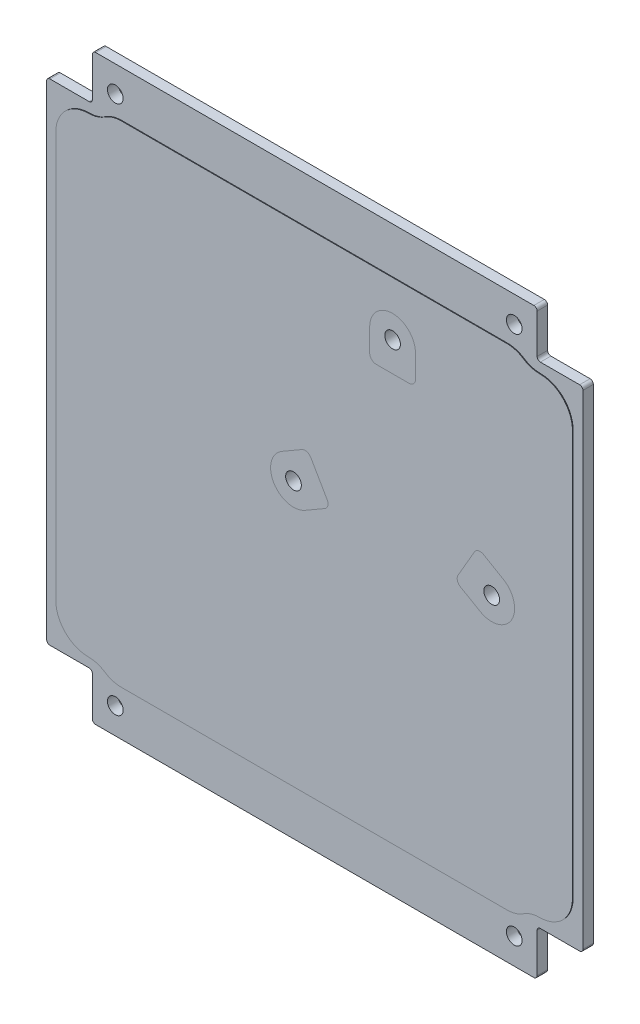
SolidWorks part; units mm, degrees
material "PET"
ref_plane "Front Plane" through (0, 0, 0) normal (0, 0, 1) x (1, 0, 0)
ref_plane "Top Plane" through (0, 0, 0) normal (0, 1, 0) x (1, 0, 0)
ref_plane "Right Plane" through (0, 0, 0) normal (1, 0, 0) x (0, 0, -1)
sketch "Sketch1" plane through (0, 0, 0) normal (0, 0, 1) x (1, 0, 0)
  line L0 (-34, 44) -> (-34, 38)
  line L1 (-33.5, -44.5) -> (33.5, -44.5)
  line L2 (-41, 37) -> (-41, -37)
  line L3 (-33.5, 44.5) -> (33.5, 44.5)
  line L4 (41, -37) -> (41, 37)
  line L5 (34, -44) -> (34, -38)
  line L6 (34.5, -37.5) -> (40.5, -37.5)
  line L7 (-34.5, 37.5) -> (-40.5, 37.5)
  line L8 (34, 44) -> (34, 38)
  line L9 (34.5, 37.5) -> (40.5, 37.5)
  line L10 (-40.5, -37.5) -> (-34.5, -37.5)
  line L11 (-34, -38) -> (-34, -44)
  line L12 (-34.5, -38) -> (34.5, 38) construction
  line L13 (34.5, -38) -> (-34.5, 38) construction
  arc A0 (-33.5, 44.5) -> (-34, 44) centre (-33.5, 44) ccw
  arc A1 (33.5, 44.5) -> (34, 44) centre (33.5, 44) cw
  arc A2 (34, 38) -> (34.5, 37.5) centre (34.5, 38) ccw
  arc A3 (40.5, 37.5) -> (41, 37) centre (40.5, 37) cw
  arc A4 (33.5, -44.5) -> (34, -44) centre (33.5, -44) ccw
  arc A5 (34.5, -37.5) -> (34, -38) centre (34.5, -38) ccw
  arc A6 (40.5, -37.5) -> (41, -37) centre (40.5, -37) ccw
  arc A7 (-34, -44) -> (-33.5, -44.5) centre (-33.5, -44) ccw
  arc A8 (-34, -38) -> (-34.5, -37.5) centre (-34.5, -38) ccw
  arc A9 (-41, -37) -> (-40.5, -37.5) centre (-40.5, -37) ccw
  arc A10 (-40.5, 37.5) -> (-41, 37) centre (-40.5, 37) ccw
  arc A11 (-34.5, 37.5) -> (-34, 38) centre (-34.5, 38) ccw
  point P0 (0, 0)
  dimension "D4" = 0.5
  dimension "D1" = 7
  dimension "D2" = 7
  dimension "D3" = 7
  dimension "D5" = 7
  dimension "D6" = 7
  dimension "D7" = 7
  dimension "D8" = 7
  dimension "D9" = 7
  dimension "D10" = 89
  dimension "D11" = 82
extrude "Boss-Extrude1" add sketch "Sketch1" along normal blind 1.6
sketch "Esboço1" plane through (0, 0, 1.6) normal (0, 0, 1) x (1, 0, 0)
  line L0 (11.8117, 0) -> (-11.978, 0) construction
  line L1 (-29.5, -37.5) -> (29.5, -37.5)
  line L2 (0, 10.1561) -> (0, -5.0161) construction
  line L3 (-29.5, 37.5) -> (29.5, 37.5)
  line L5 (-29.5, -32.5) -> (29.5, 32.5) construction
  line L6 (-29.5, 32.5) -> (29.5, -32.5) construction
  line L8 (-39.5, -31) -> (-39.5, 31)
  line L10 (39.5, -31) -> (39.5, 31)
  line L11 (-39.5, -36) -> (39.5, 36) construction
  line L12 (-39.5, 36) -> (39.5, -36) construction
  arc A0 (-34.5, 36) -> (-32, 36.75) centre (-34.5, 40.5417) ccw
  arc A1 (-29.5, 37.5) -> (-32, 36.75) centre (-29.5, 32.9583) ccw
  arc A2 (-29.5, -37.5) -> (-32, -36.75) centre (-29.5, -32.9583) cw
  arc A3 (-34.5, -36) -> (-32, -36.75) centre (-34.5, -40.5417) cw
  arc A4 (34.5, 36) -> (39.5, 31) centre (34.5, 31) cw
  arc A5 (34.5, -36) -> (39.5, -31) centre (34.5, -31) ccw
  arc A6 (-34.5, -36) -> (-39.5, -31) centre (-34.5, -31) cw
  arc A7 (-39.5, 31) -> (-34.5, 36) centre (-34.5, 31) cw
  arc A8 (29.5, -37.5) -> (32, -36.75) centre (29.5, -32.9583) ccw
  arc A9 (34.5, -36) -> (32, -36.75) centre (34.5, -40.5417) ccw
  arc A10 (29.5, 37.5) -> (32, 36.75) centre (29.5, 32.9583) cw
  arc A11 (34.5, 36) -> (32, 36.75) centre (34.5, 40.5417) cw
  point P0 (0, 0)
  point P1 (0, 0)
  dimension "D2" = 5
  dimension "D3" = 75
  dimension "D5" = 79
extrude "Boss-Extrude2" add sketch "Esboço1" along normal blind 0.1
hole_wizard "M2 Hole1-FixingStructure" positions "Sketch3" profile "Sketch2" hole size "M2" standard "DIN"
sketch "Sketch3" plane through (0, 0, 0) normal (0, 0, -1) x (-1, 0, 0)
  line L0 (-33.5, 44.5) -> (33.5, 44.5) construction
  line L1 (33.5, -44.5) -> (-33.5, -44.5) construction
  line L2 (-41, -37) -> (-41, 37) construction
  line L3 (41, 37) -> (41, -37) construction
  point P0 (-30.5, 40.5)
  point P2 (30.5, 40.5)
  point P4 (-30.5, -40.5)
  point P6 (30.5, -40.5)
  dimension "D1" = 4
  dimension "D2" = 4
  dimension "D3" = 10.5
  dimension "D4" = 10.5
sketch "Sketch2" plane through (30.5, 40.5, 0) normal (1, 0, 0) x (0, 1, 0)
  line L0 (0, 0) -> (0, 200.721)
  line L1 (0, 200.721) -> (1.2, 200)
  line L2 (1.2, 200) -> (1.2, 0)
  line L5 (1.2, 0) -> (0, 0)
  line L10 (0, 200.721) -> (-1.2, 200) construction
  line L11 (0, -6.35) -> (0, 107.95) construction
  dimension "Hole Dia." = 2.4
  dimension "Hole Depth" = 200
  dimension "Drill Angle" = 118
sketch "Sketch4" plane through (0, 0, 1.7) normal (0, 0, 1) x (1, 0, 0)
  circle A0 centre (27.1554, 3) radius 1.2 construction
  circle A1 centre (-3.1554, 3) radius 1.2 construction
  circle A2 centre (12, 29.25) radius 1.2 construction
  circle A3 centre (27.1554, 3) radius 1.2
  circle A4 centre (-3.1554, 3) radius 1.2
  circle A5 centre (12, 29.25) radius 1.2
extrude "Cut-Extrude1" cut sketch "Sketch4" against normal up to surface (1.7 mm away) up to face at (29.3, 40.5, 0)
sketch "Sketch5" plane through (0, 0, 1.7) normal (0, 0, 1) x (1, 0, 0)
  line L4 (1.6256, 1.7189) -> (-1.4054, -0.0311)
  line L5 (26.7404, 7.2811) -> (28.9054, 6.0311)
  line L6 (25.4054, -0.0311) -> (23.2404, 1.2189)
  line L7 (25.8744, 7.7811) -> (28.9054, 6.0311)
  line L8 (25.4054, -0.0311) -> (22.3744, 1.7189)
  line L9 (22.0083, 3.0849) -> (24.5083, 7.4151)
  line L10 (22.0083, 3.0849) -> (24.5083, 7.4151)
  line L11 (-4.9054, 6.0311) -> (-1.8744, 7.7811)
  line L12 (-0.5083, 7.4151) -> (1.9917, 3.0849)
  line L13 (8.5, 25.75) -> (8.5, 29.25)
  line L14 (15.5, 29.25) -> (15.5, 25.75)
  line L15 (14.5, 24.75) -> (9.5, 24.75)
  arc A3 (22.3744, 1.7189) -> (22.0083, 3.0849) centre (22.8744, 2.5849) cw
  arc A4 (25.4054, -0.0311) -> (28.9054, 6.0311) centre (27.1554, 3) ccw
  arc A5 (25.4054, -0.0311) -> (28.9054, 6.0311) centre (27.1554, 3) ccw
  arc A6 (25.8744, 7.7811) -> (24.5083, 7.4151) centre (25.3744, 6.9151) ccw
  circle A7 centre (12, 11.75) radius 4.1 construction
  arc A8 (-1.8744, 7.7811) -> (-0.5083, 7.4151) centre (-1.3744, 6.9151) cw
  arc A9 (-4.9054, 6.0311) -> (-1.4054, -0.0311) centre (-3.1554, 3) ccw
  arc A10 (1.6256, 1.7189) -> (1.9917, 3.0849) centre (1.1256, 2.5849) ccw
  arc A11 (15.5, 25.75) -> (14.5, 24.75) centre (14.5, 25.75) cw
  arc A12 (15.5, 29.25) -> (8.5, 29.25) centre (12, 29.25) ccw
  arc A13 (8.5, 25.75) -> (9.5, 24.75) centre (9.5, 25.75) ccw
  point P13 (12, 11.75)
  point P37 (12, 11.75)
  dimension "D3" = 1
  dimension "D1" = 1
  dimension "D2" = 1
  dimension "D4" = 3
split line "Split Line1"
